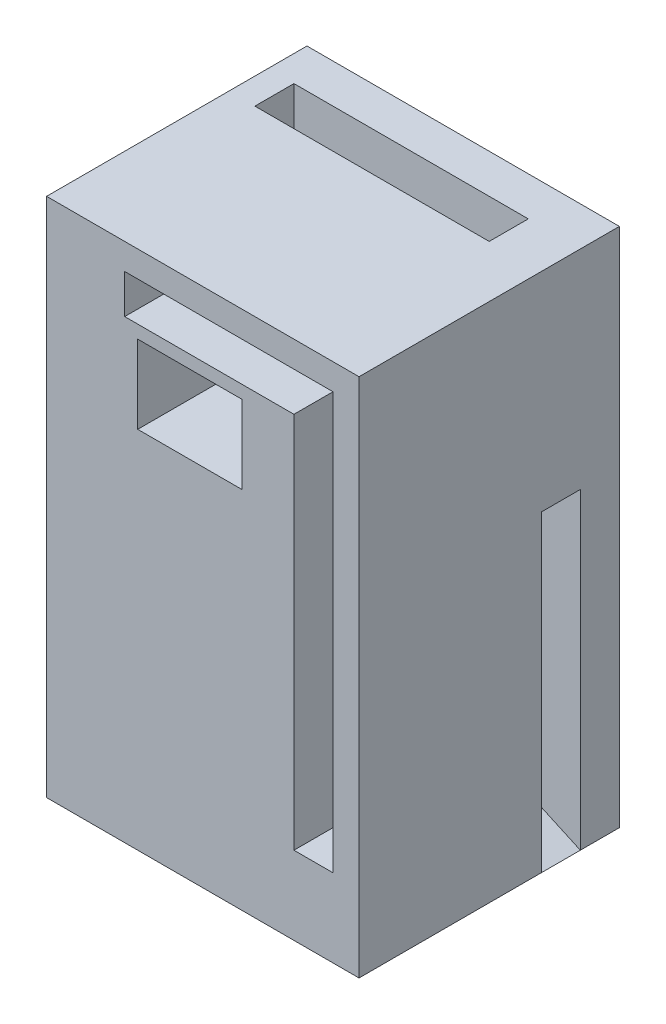
SolidWorks part; units mm, degrees
ref_plane "Front Plane" through (0, 0, 0) normal (0, 0, 1) x (1, 0, 0)
ref_plane "Top Plane" through (0, 0, 0) normal (0, 1, 0) x (1, 0, 0)
ref_plane "Right Plane" through (0, 0, 0) normal (1, 0, 0) x (0, 0, -1)
sketch "Sketch1" plane through (0, 0, 0) normal (0, 0, 1) x (1, 0, 0)
  line L0 (0, 0) -> (55, 0)
  line L1 (0, 0) -> (-5, 0)
  line L3 (0, 25) -> (-5, 25)
  line L4 (-5, 0) -> (-5, 25)
  line L5 (55, 0) -> (0, 25)
  point P5 (0, 0)
  point P7 (0, 0)
  point P8 (0, 0)
  point P9 (0, 0)
  dimension "D1" = 5
  dimension "D2" = 25
  dimension "D3" = 60
extrude "Boss-Extrude1" add sketch "Sketch1" along normal mid plane 50
sketch "Sketch2" plane through (0, 0, 0) normal (0, 1, 0) x (1, 0, 0)
  line L1 (55, -25) -> (-5, -25)
  line L2 (55, -25) -> (55, 10)
  line L3 (55, 10) -> (-5, 10)
  line L4 (-5, -25) -> (-5, 10)
  line L5 (55, -25) -> (55, 25) construction
  line L6 (-5, 25) -> (55, 25)
  line L7 (-5, 25) -> (-5, 17.5)
  line L8 (-5, 17.5) -> (55, 17.5)
  line L9 (55, 25) -> (55, 17.5)
  line L10 (-5, -25) -> (-5, 25) construction
  dimension "D1" = 35
  dimension "D2" = 7.5
extrude "Boss-Extrude2" add sketch "Sketch2" along normal blind 100
sketch "Sketch3" plane through (0, 25, 0) normal (0, 1, 0) x (1, 0, 0)
  line L1 (-5, 17.5) -> (0, 17.5)
  line L2 (-5, 17.5) -> (-5, 10)
  line L3 (-5, 10) -> (0, 10)
  line L4 (0, 17.5) -> (0, 10)
extrude "Boss-Extrude3" add sketch "Sketch3" along normal up to surface (75 mm away) up to face at (25, 100, -21.25)
sketch "Sketch4" plane through (0, 0, -17.5) normal (0, 0, 1) x (1, 0, 0)
  line L0 (-5, 0) -> (55, 0) construction
  line L1 (55, 100) -> (45, 100)
  line L2 (55, 100) -> (55, 60)
  line L3 (55, 60) -> (45, 60)
  line L4 (45, 100) -> (45, 60)
  dimension "D1" = 10
  dimension "D2" = 40
extrude "Boss-Extrude4" add sketch "Sketch4" along normal up to surface (7.5 mm away) up to face at (27.5, 56.25, -10)
sketch "Sketch5" plane through (0, 0, 25) normal (0, 0, 1) x (1, 0, 0)
  line L0 (45, 100) -> (0, 100) construction
  line L1 (12.5, 70) -> (32.5, 70)
  line L2 (12.5, 70) -> (12.5, 85)
  line L3 (12.5, 85) -> (32.5, 85)
  line L4 (32.5, 70) -> (32.5, 85)
  line L6 (-5, 100) -> (55, 100) construction
  point P6 (22.5, 100)
  point P7 (22.5, 85)
  dimension "D1" = 15
  dimension "D2" = 20
  dimension "D3" = 15
extrude "Cut-Extrude1" cut sketch "Sketch5" against normal up to next
sketch "Sketch7" plane through (0, 0, 25) normal (0, 0, 1) x (1, 0, 0)
  line L0 (-5, 100) -> (55, 100) construction
  line L1 (55, 100) -> (55, 0) construction
  line L2 (-5, 100) -> (-5, 0) construction
  line L3 (-5, 0) -> (55, 0) construction
  line L5 (10, 95) -> (50, 95)
  line L6 (10, 95) -> (10, 87.5)
  line L7 (10, 87.5) -> (42.5, 87.5)
  line L30 (50, 95) -> (50, 15)
  line L31 (50, 15) -> (42.5, 15)
  line L32 (42.5, 87.5) -> (42.5, 15)
  point P7 (0, 0)
  point P8 (0, 0)
  point P9 (0, 0)
  dimension "D1" = 7.5
  dimension "D2" = 5
  dimension "D3" = 5
  dimension "D4" = 15
  dimension "D5" = 15
extrude "Cut-Extrude2" cut sketch "Sketch7" against normal blind 15
